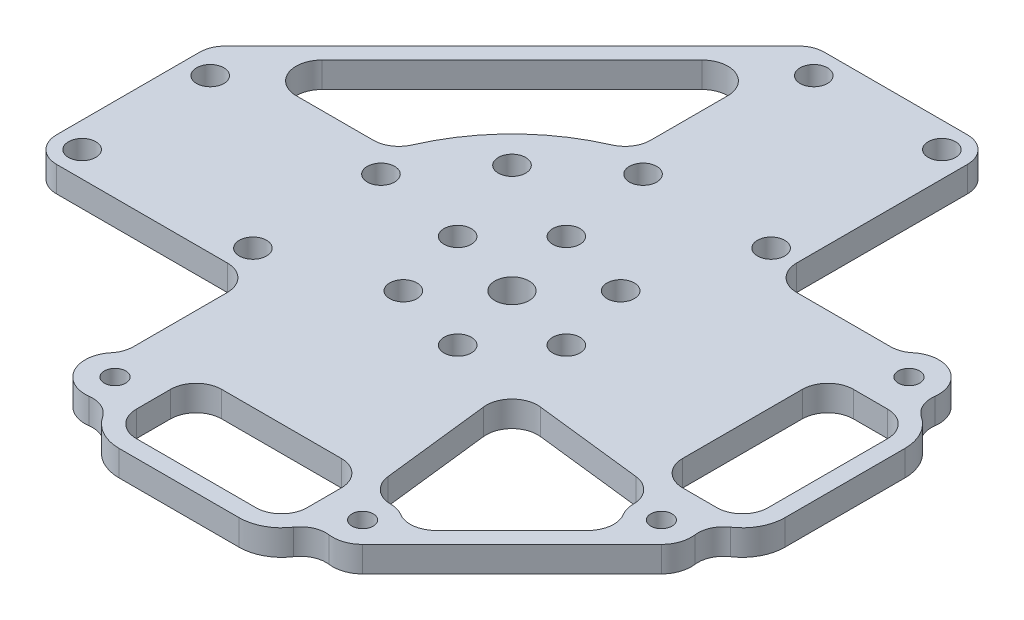
SolidWorks part; units mm, degrees
material "6061-T6 (SS)"
ref_plane "Front Plane" through (0, 0, 0) normal (0, 0, 1) x (1, 0, 0)
ref_plane "Top Plane" through (0, 0, 0) normal (0, 1, 0) x (1, 0, 0)
ref_plane "Right Plane" through (0, 0, 0) normal (1, 0, 0) x (0, 0, -1)
sketch "Sketch1" plane through (0, 0, 0) normal (0, 1, 0) x (1, 0, 0)
  line L0 (-14.5, -32) -> (14.5, -32) construction
  line L1 (10.85, 19.5) -> (-4.15, 19.5)
  line L2 (10.85, 19.5) -> (10.85, 39.5)
  line L3 (10.85, 39.5) -> (-4.15, 39.5)
  line L4 (-4.15, 19.5) -> (-4.15, 39.5)
  line L5 (10.85, 19.5) -> (-4.15, 39.5) construction
  line L6 (10.85, 39.5) -> (-4.15, 19.5) construction
  line L7 (-19.5, -10.85) -> (-39.5, -10.85)
  line L8 (-19.5, -10.85) -> (-19.5, 4.15)
  line L9 (-19.5, 4.15) -> (-39.5, 4.15)
  line L10 (-39.5, -10.85) -> (-39.5, 4.15)
  line L11 (-19.5, -10.85) -> (-39.5, 4.15) construction
  line L12 (-19.5, 4.15) -> (-39.5, -10.85) construction
  line L13 (20.7, 16) -> (-14, 16)
  line L14 (20.7, 16) -> (20.7, 43)
  line L15 (20.7, 43) -> (-14, 43)
  line L16 (-14, 16) -> (-14, 43)
  line L17 (20.7, 16) -> (-14, 43) construction
  line L18 (20.7, 43) -> (-14, 16) construction
  line L19 (-16, -20.7) -> (-43, -20.7)
  line L20 (-16, -20.7) -> (-16, 14)
  line L21 (-16, 14) -> (-43, 14)
  line L22 (-43, -20.7) -> (-43, 14)
  line L23 (-16, -20.7) -> (-43, 14) construction
  line L24 (-16, 14) -> (-43, -20.7) construction
  line L25 (10, -37) -> (-10, -37)
  line L26 (10, -37) -> (10, -27)
  line L27 (10, -27) -> (-10, -27)
  line L28 (-10, -37) -> (-10, -27)
  line L29 (10, -37) -> (-10, -27) construction
  line L30 (10, -27) -> (-10, -37) construction
  line L31 (37, -10) -> (27, -10)
  line L32 (37, -10) -> (37, 10)
  line L33 (37, 10) -> (27, 10)
  line L34 (27, -10) -> (27, 10)
  line L35 (37, -10) -> (27, 10) construction
  line L36 (37, 10) -> (27, -10) construction
  line L37 (32, 14.5) -> (32, -14.5) construction
  circle A0 centre (0, 0) radius 2
  circle A1 centre (0, 0) radius 9
  circle A2 centre (0, 0) radius 12.7
  point P3 (3.35, 29.5)
  point P8 (-29.5, -3.35)
  point P15 (0, -32)
  point P16 (-29.5, -3.35)
  point P17 (3.35, 29.5)
  point P30 (32, 0)
  point P38 (0, -32)
  point P41 (32, 0)
  dimension "D1" = 4
  dimension "D4" = 18
  dimension "D11" = 25.4
  dimension "D2" = 20
  dimension "D3" = 15
  dimension "D5" = 34.7
  dimension "D6" = 27
  dimension "D7" = 2
  dimension "D8" = 2
  dimension "D9" = 16
  dimension "D10" = 16
  dimension "D12" = 32
  dimension "D13" = 10
  dimension "D14" = 20
  dimension "D15" = 32
  dimension "D16" = 4.5
sketch "Sketch2" plane through (0, 0, 0) normal (0, 1, 0) x (1, 0, 0)
  line L3 (-16.5, -13.85) -> (-42.5, -13.85)
  line L4 (-42.5, -13.85) -> (-42.5, 7.15)
  line L5 (-42.5, 7.15) -> (-24.825, 24.825)
  line L6 (-19.5, -10.85) -> (-39.5, -10.85) construction
  line L9 (-39.5, -10.85) -> (-39.5, 4.15) construction
  line L10 (-19.5, -10.85) -> (-19.5, 4.15) construction
  line L12 (-19.5, 4.15) -> (-39.5, 4.15) construction
  line L16 (-16.5, -13.85) -> (-16.5, -29.1277)
  line L22 (16.9749, -34.4749) -> (25.7249, -25.7249)
  line L29 (25.7249, -25.7249) -> (-24.825, 24.825)
  line L39 (12, -27) -> (12, -39)
  line L40 (12, -39) -> (-12, -39)
  line L41 (-12, -39) -> (-12, -27)
  line L42 (12, -34.4495) -> (12, -39)
  line L43 (12, -39) -> (-12, -39)
  line L44 (-12, -39) -> (-12, -34.4495)
  arc A0 (-16.5, -29.1277) -> (-12, -34.4495) centre (-14.5, -32) ccw
  arc A2 (12, -34.4495) -> (16.9749, -34.4749) centre (14.5, -32) ccw
  dimension "D1" = 7
  dimension "D2" = 3
  dimension "D3" = 45
  dimension "D4" = 2
  dimension "D5" = 3
  dimension "D6" = 3
  dimension "D8" = 3
extrude "Boss-Extrude1" add sketch "Sketch2" along normal blind 3
mirror "Mirror5" about plane through (25.7249, 3, 25.7249) normal (-0.7071, 0, 0.7071) of bodies 101
hole_wizard "M3 Clearance Hole1" positions "Sketch3" profile "Sketch4" hole size "M3" standard "ANSI Metric" end condition up to next
sketch "Sketch3" plane through (0, 3, 0) normal (0, 1, 0) x (1, 0, 0)
  point P0 (-39.5, 4.15)
  point P3 (-19.5, 4.15)
  point P6 (-19.5, -10.85)
  point P9 (-39.5, -10.85)
  point P12 (-4.15, 19.5)
  point P15 (-4.15, 39.5)
  point P18 (10.85, 39.5)
  point P21 (10.85, 19.5)
sketch "Sketch4" plane through (-39.5, 3, -4.15) normal (1, 0, 0) x (0, 0, 1)
  line L0 (0, 0) -> (0, 3)
  line L1 (0, 3) -> (1.6, 3)
  line L2 (1.6, 3) -> (1.6, 0)
  line L5 (1.6, 0) -> (0, 0)
  line L11 (0, -6.35) -> (0, 107.95) construction
  dimension "Thru Hole Dia." = 3.2
  dimension "Thru Hole Depth" = 3
hole_wizard "M3 Clearance Hole2" positions "Sketch5" profile "Sketch6" hole size "M3" standard "ANSI Metric" end condition up to next
sketch "Sketch5" plane through (0, 3, 0) normal (0, 1, 0) x (1, 0, 0)
  line L4 (-8.6933, 2.3294) -> (-2.3294, 8.6933) construction
  line L5 (0, 0) -> (-5.5114, 5.5114) construction
  line L7 (-1000, 0) -> (49000, 0) construction
  circle A0 centre (0, 0) radius 9 construction
  point P23 (-2.3294, 8.6933)
  point P46 (6.364, 6.364)
  point P47 (8.6933, -2.3294)
  point P48 (2.3294, -8.6933)
  point P49 (-6.364, -6.364)
  point P50 (-8.6933, 2.3294)
  dimension "D1" = 45
  dimension "D2" = 6
sketch "Sketch6" plane through (-2.3294, 3, -8.6933) normal (1, 0, 0) x (0, 0, 1)
  line L0 (0, 0) -> (0, 3)
  line L1 (0, 3) -> (1.6, 3)
  line L2 (1.6, 3) -> (1.6, 0)
  line L5 (1.6, 0) -> (0, 0)
  line L11 (0, -6.35) -> (0, 107.95) construction
  dimension "Thru Hole Dia." = 3.2
  dimension "Thru Hole Depth" = 3
hole_wizard "Ø4.0 (4) Diameter Hole1" positions "Sketch7" profile "Sketch8" hole size "Ø4.0" standard "ANSI Metric" end condition up to next
sketch "Sketch7" plane through (0, 3, 0) normal (0, 1, 0) x (1, 0, 0)
  point P0 (0, 0)
sketch "Sketch8" plane through (0, 3, 0) normal (1, 0, 0) x (0, 0, 1)
  line L0 (0, 0) -> (0, 3)
  line L1 (0, 3) -> (2, 3)
  line L2 (2, 3) -> (2, 0)
  line L5 (2, 0) -> (0, 0)
  line L11 (0, -6.35) -> (0, 107.95) construction
  dimension "Thru Hole Dia." = 4
  dimension "Thru Hole Depth" = 3
hole_wizard "Tap Drill for M3x0.5 Tap1" positions "Sketch10" profile "Sketch11" hole size "M3x0.5" standard "ANSI Metric" end condition up to next
sketch "Sketch10" plane through (0, 0, 0) normal (0, -1, 0) x (-1, 0, 0)
  point P0 (-14.5, -32)
  point P3 (14.5, -32)
  point P6 (-32, -14.5)
  point P9 (-32, 14.5)
sketch "Sketch11" plane through (14.5, 0, 32) normal (1, 0, 0) x (0, 0, -1)
  line L0 (0, 0) -> (0, 3)
  line L1 (0, 3) -> (1.25, 3)
  line L2 (1.25, 3) -> (1.25, 0)
  line L5 (1.25, 0) -> (0, 0)
  line L11 (0, -6.35) -> (0, 107.95) construction
  dimension "Thru Hole Dia." = 2.5
  dimension "Thru Hole Depth" = 3
sketch "Sketch9" plane through (0, 3, 0) normal (0, 1, 0) x (1, 0, 0)
  line L0 (27, -10) -> (27, 10) construction
  line L1 (37, 10) -> (27, 10) construction
  line L2 (37, -10) -> (37, 10) construction
  line L3 (37, -10) -> (27, -10) construction
  line L4 (10, -27) -> (-10, -27) construction
  line L5 (10, -37) -> (10, -27) construction
  line L6 (10, -37) -> (-10, -37) construction
  line L7 (-10, -37) -> (-10, -27) construction
  line L8 (27, -10) -> (27, 10)
  line L9 (37, 10) -> (27, 10)
  line L10 (37, -10) -> (37, 10)
  line L11 (37, -10) -> (27, -10)
  line L12 (10, -27) -> (-10, -27)
  line L13 (10, -37) -> (10, -27)
  line L14 (10, -37) -> (-10, -37)
  line L15 (-10, -37) -> (-10, -27)
extrude "Cut-Extrude1" cut sketch "Sketch9" against normal up to surface (3 mm away) up to face at (0, 0, 2)
fillet "Fillet1" radius 3 8 edges at (37, 1.5, -10) (37, 1.5, 10) (27, 1.5, 10) (27, 1.5, -10) (-10, 1.5, 37) (10, 1.5, 37) (10, 1.5, 27) (-10, 1.5, 27)
fillet "Fillet2" radius 5 4 edges at (39, 1.5, -12) (39, 1.5, 12) (12, 1.5, 39) (-12, 1.5, 39)
fillet "Fillet3" radius 3 12 edges at (34.4495, 1.5, 12) (12, 1.5, 34.4495) (-12, 1.5, 34.4495) (-16.5, 1.5, 29.1277) (-16.5, 1.5, 13.85) (-42.5, 1.5, -7.15) (-7.15, 1.5, -42.5) (13.85, 1.5, -42.5) (13.85, 1.5, -16.5) (29.1277, 1.5, -16.5) (34.4495, 1.5, -12) (-42.5, 1.5, 13.85)
sketch "Sketch12" plane through (0, 3, 0) normal (0, 1, 0) x (1, 0, 0)
  line L2 (15.5607, -33.0607) -> (33.0607, -15.5607)
  line L3 (17.5993, -31.022) -> (31.022, -17.5993)
  line L13 (12, -34) -> (12, -30)
  line L15 (11.967, -29.4264) -> (9.6874, -9.6874)
  line L16 (30, -12) -> (34, -12)
  line L18 (0, 0) -> (9.6874, -9.6874) construction
  line L20 (9.6874, -9.6874) -> (29.4264, -11.967)
  circle A2 centre (14.5, -32) radius 3.25
  arc A3 (17.5993, -31.022) -> (11.9994, -29.924) centre (14.5, -32) ccw
  circle A5 centre (32, -14.5) radius 3.25
  arc A6 (29.924, -11.9994) -> (31.022, -17.5993) centre (32, -14.5) ccw
  arc A17 (12, -30) -> (7, -25) centre (7, -30) ccw
  arc A18 (11.9994, -29.924) -> (11.967, -29.4264) centre (7, -30) ccw
  circle A19 centre (0, 0) radius 13.7 construction
  arc A20 (25, -7) -> (30, -12) centre (30, -7) ccw
  arc A21 (29.4264, -11.967) -> (29.924, -11.9994) centre (30, -7) ccw
  dimension "D4" = 27.4
  dimension "D1" = 2
  dimension "D2" = 2
  dimension "D3" = 2
  dimension "D5" = 2
  dimension "D6" = 2
extrude "Cut-Extrude2" cut sketch "Sketch12" against normal up to surface (3 mm away) up to face at (32, 0, 0)
fillet "Fillet4" radius 3 5 edges at (17.5993, 1.5, 31.022) (11.9994, 1.5, 29.924) (31.022, 1.5, 17.5993) (29.924, 1.5, 11.9994) (9.6874, 1.5, 9.6874)
sketch "Sketch13" plane through (0, 3, 0) normal (0, 1, 0) x (1, 0, 0)
  line L0 (-39.6716, 7.15) -> (-21.3337, 7.15)
  line L1 (0, 0) -> (-24.825, 24.825) construction
  line L2 (-8.0287, 41.6213) -> (-41.6213, 8.0287) construction
  line L4 (-23.4108, 23.4108) -> (-15.9099, 15.9099)
  line L5 (-6.6145, 40.2071) -> (-40.2071, 6.6145)
  line L6 (-23.4108, 23.4108) -> (-39.6716, 7.15)
  circle A2 centre (0, 0) radius 22.5 construction
  circle A3 centre (-19.5, 4.15) radius 1.6 construction
  arc A4 (-21.3337, 7.15) -> (-15.9099, 15.9099) centre (0, 0) cw
  dimension "D1" = 45
  dimension "D2" = 3
  dimension "D3" = 2
extrude "Cut-Extrude3" cut sketch "Sketch13" against normal up to surface (3 mm away) contours L0 A4 L4 L6 region at (-26.206, 3, -13.3731) up to face at (32, 0, 0)
mirror "Mirror6" about plane through (0, -28.7929, 0) normal (-0.7071, 0, 0.7071) of "Cut-Extrude3"
fillet "Fillet5" radius 3 4 edges at (-7.15, 1.5, -39.6716) (-7.15, 1.5, -21.3337) (-21.3337, 1.5, -7.15) (-39.6716, 1.5, -7.15)
hole_wizard "M3 Clearance Hole3" positions "Sketch14" profile "Sketch15" hole size "M3" standard "ANSI Metric" end condition up to next
sketch "Sketch14" plane through (0, 3, 0) normal (0, 1, 0) x (1, 0, 0)
  line L0 (-12.7279, 12.7279) -> (0, 0) construction
  line L2 (-12.2713, 34.5503) -> (-34.5503, 12.2713) construction
  circle A2 centre (-12.7279, 12.7279) radius 3
  point P0 (-12.7279, 12.7279)
  dimension "D1" = 6
  dimension "D2" = 18
sketch "Sketch15" plane through (-12.7279, 3, -12.7279) normal (1, 0, 0) x (0, 0, 1)
  line L0 (0, 0) -> (0, 3)
  line L1 (0, 3) -> (1.6, 3)
  line L2 (1.6, 3) -> (1.6, 0)
  line L5 (1.6, 0) -> (0, 0)
  line L11 (0, -6.35) -> (0, 107.95) construction
  dimension "Thru Hole Dia." = 3.2
  dimension "Thru Hole Depth" = 3
